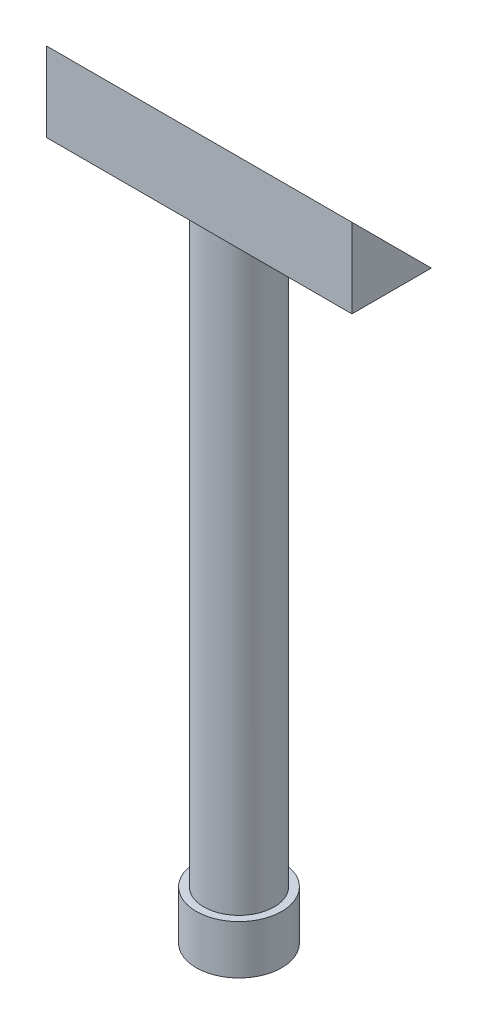
SolidWorks part; units mm, degrees
ref_plane "Front Plane" through (0, 0, 0) normal (0, 0, 1) x (1, 0, 0)
ref_plane "Top Plane" through (0, 0, 0) normal (0, 1, 0) x (1, 0, 0)
ref_plane "Right Plane" through (0, 0, 0) normal (1, 0, 0) x (0, 0, -1)
sketch "Sketch1" plane through (0, 0, 0) normal (0, 1, 0) x (1, 0, 0)
  circle A0 centre (0, 0) radius 7
  circle A1 centre (0, 0) radius 4.75
  circle A2 centre (0, 0) radius 4
  dimension "D1" = 8
  dimension "D2" = 9.5
  dimension "D3" = 14
extrude "Boss-Extrude1" add sketch "Sketch1" along normal blind 8 contours A0 A1 | A1 A2 region at (-6.802, 0, 0) region at (-4.6156, 0, 0)
extrude "Boss-Extrude2" add sketch "Sketch1<3>" along normal blind 80 contours A1 A2 region at (-4.6156, 0, 0)
sketch "Sketch1<3>" plane through (0, 0, 0) normal (0, 1, 0) x (1, 0, 0) same geometry as "Sketch1"
sketch "Sketch3" plane through (0, 0, 0) normal (0, -1, 0) x (1, 0, 0)
  circle A0 centre (0, 0) radius 3.05
  circle A1 centre (0, 0) radius 5.75
  dimension "D1" = 6.1
extrude "Boss-Extrude3" add sketch "Sketch3" against normal blind 105
sketch "Sketch8" plane through (0, 105, 0) normal (0, 1, 0) x (1, 0, 0)
  line L1 (-25, 6.5) -> (25, 6.5)
  line L2 (-25, 6.5) -> (-25, -6.5)
  line L3 (-25, -6.5) -> (25, -6.5)
  line L4 (25, 6.5) -> (25, -6.5)
  line L5 (-25, 6.5) -> (25, -6.5) construction
  line L6 (-25, -6.5) -> (25, 6.5) construction
  point P0 (0, 0)
  dimension "D1" = 50
  dimension "D2" = 13
extrude "Boss-Extrude8" add sketch "Sketch8" along normal blind 4
sketch "Sketch9" plane through (0, 109, 0) normal (0, 1, 0) x (1, 0, 0)
  line L1 (25, -0.254) -> (-25, -0.254)
  line L2 (25, -0.254) -> (25, -6.5)
  line L3 (25, -6.5) -> (-25, -6.5)
  line L4 (-25, -0.254) -> (-25, -6.5)
  line L5 (25, -0.254) -> (-25, -6.5) construction
  line L6 (25, -6.5) -> (-25, -0.254) construction
  point P0 (0, -3.377)
extrude "Boss-Extrude9" add sketch "Sketch9" along normal blind 9
sketch "Sketch10" plane through (-25, 0, 0) normal (-1, 0, 0) x (0, 0, 1)
  line L0 (0.254, 118) -> (0.254, 109)
  line L1 (0.254, 109) -> (-6.5, 109)
  arc A0 (0.254, 118) -> (-6.5, 109) centre (1.377, 110.123) ccw
extrude "Boss-Extrude10" add sketch "Sketch10" against normal blind 50
sketch "Sketch11" plane through (0, 118, 0) normal (0, 1, 0) x (1, 0, 0)
  line L0 (-25, -0.254) -> (-25, -6.5) construction
  line L1 (25, 6.4913) -> (-25, 6.4913)
  line L2 (25, 6.4913) -> (25, -6.4913)
  line L3 (25, -6.4913) -> (-25, -6.4913)
  line L4 (-25, 6.4913) -> (-25, -6.4913)
  line L5 (25, 6.4913) -> (-25, -6.4913) construction
  line L6 (25, -6.4913) -> (-25, 6.4913) construction
  point P0 (0, 0)
extrude "Boss-Extrude11" add sketch "Sketch11" against normal blind 10
sketch "Sketch12" plane through (0, 0, -6.4913) normal (0, 0, -1) x (-1, 0, 0)
  line L0 (-25, 118) -> (25, 118)
  line L1 (-25, 118) -> (25, 118) construction
  line L2 (25, 111.3052) -> (25, 118) construction
  arc A0 (-25, 118) -> (25, 118) centre (0, 283.6596) ccw
extrude "Cut-Extrude1" cut sketch "Sketch12" against normal blind 100
sketch "Sketch13" plane through (0, 105, 0) normal (0, -1, 0) x (1, 0, 0)
  line L1 (25, 6.5) -> (-25, 6.5)
  line L2 (25, 6.5) -> (25, -6.5)
  line L3 (25, -6.5) -> (-25, -6.5)
  line L4 (-25, 6.5) -> (-25, -6.5)
  line L5 (25, 6.5) -> (-25, -6.5) construction
  line L6 (25, -6.5) -> (-25, 6.5) construction
  point P0 (0, 0)
extrude "Boss-Extrude12" add sketch "Sketch13" against normal blind 13
sketch "Sketch14" plane through (-25, 0, 0) normal (-1, 0, 0) x (0, 0, 1)
  line L0 (-6.5, 105) -> (6.5, 118)
  line L1 (6.5, 118) -> (-6.5, 118)
  line L2 (-6.5, 118) -> (-6.5, 107)
  line L3 (-6.5, 109) -> (-6.5, 105) construction
  line L4 (-6.5, 107) -> (-6.5, 105)
extrude "Cut-Extrude2" cut sketch "Sketch14" against normal blind 50
sketch "Sketch15" plane through (-25, 0, 0) normal (-1, 0, 0) x (0, 0, 1)
  line L0 (6.5, 118) -> (-6.5, 105)
  line L1 (-6.5, 105) -> (-15.0468, 116.294)
  line L2 (-15.0468, 116.294) -> (5.8115, 117.9531)
  arc A0 (5.8115, 117.9531) -> (6.5, 118) centre (8.2068, 87.8413) cw
extrude "Cut-Extrude3" cut sketch "Sketch15" against normal blind 50
